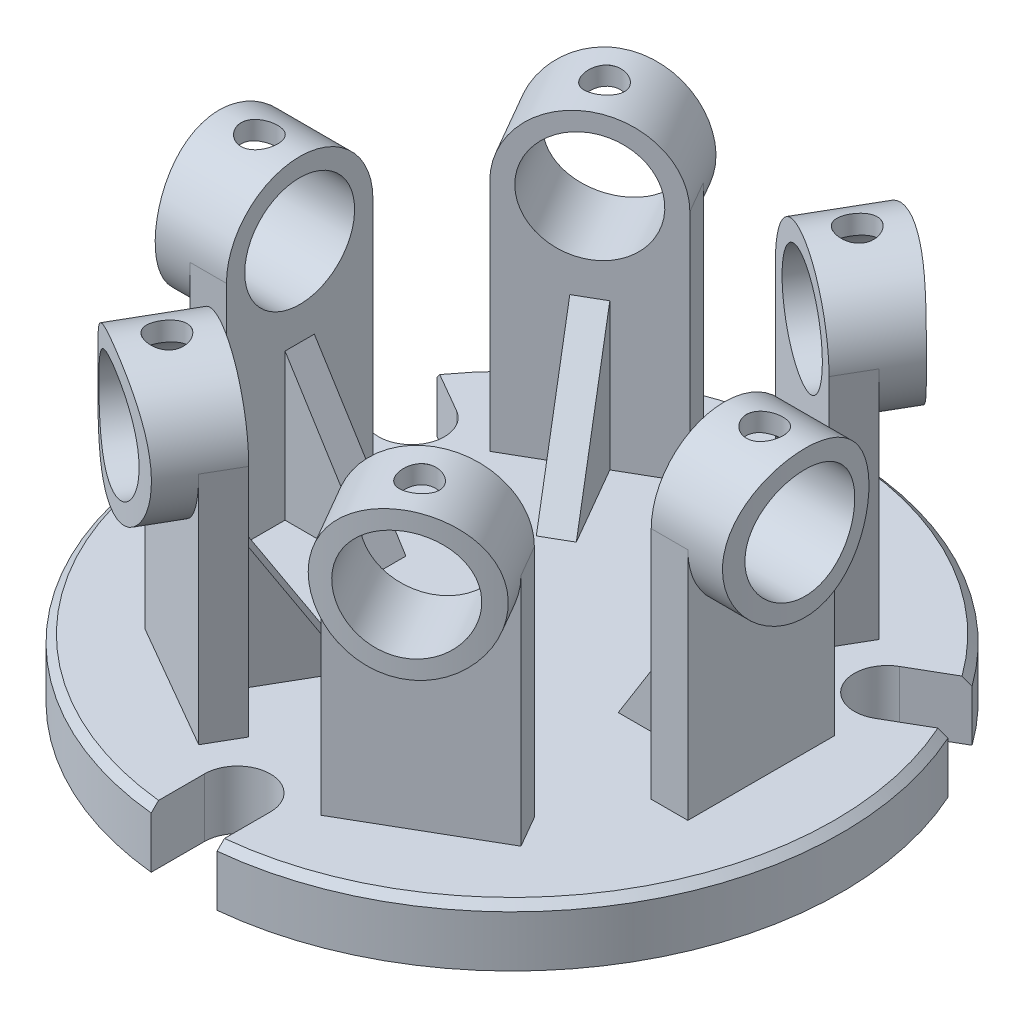
SolidWorks part; units mm, degrees
ref_plane "Front Plane" through (0, 0, 0) normal (0, 0, 1) x (1, 0, 0)
ref_plane "Top Plane" through (0, 0, 0) normal (0, 1, 0) x (1, 0, 0)
ref_plane "Right Plane" through (0, 0, 0) normal (1, 0, 0) x (0, 0, -1)
sketch "Sketch1" plane through (0, 0, 0) normal (0, 1, 0) x (1, 0, 0)
  circle A0 centre (0, 0) radius 90
  dimension "D1" = 180
extrude "Boss-Extrude1" add sketch "Sketch1" along normal blind 16
sketch "Sketch16" plane through (0, 16, 0) normal (0, 1, 0) x (1, 0, 0)
  line L0 (0, 0) -> (0, -90) construction
  line L1 (-9, -75) -> (-9, -89.5489)
  line L2 (9, -75) -> (9, -89.5489)
  circle A0 centre (0, 0) radius 90 construction
  arc A1 (9, -75) -> (-9, -75) centre (0, -75) ccw
  arc A2 (-9, -89.5489) -> (9, -89.5489) centre (0, 0) ccw
  dimension "D1" = 18
  dimension "D2" = 75
extrude "Cut-Extrude4" cut sketch "Sketch16" against normal up to next
pattern_circular "CirPattern12" count 3 over 360 about axis through (0, 16, 0) along (0, -1, 0) of "Cut-Extrude4" reverse direction yes
sketch "Sketch2" plane through (0, 0, 0) normal (0, 0, 1) x (1, 0, 0)
  line L0 (0, 0) -> (-90, 0) construction
  line L2 (-33, 16) -> (-58, 16)
  line L4 (-58, 16) -> (-58, 56)
  line L5 (-58, 56) -> (-33, 16)
  point P2 (-90, 0)
  point P6 (-33, 16)
  dimension "D1" = 16
  dimension "D2" = 25
  dimension "D3" = 40
  dimension "D4" = 58
extrude "Boss-Extrude2" add sketch "Sketch2" along normal blind 4 and the other way blind 4
sketch "Sketch6" plane through (-58, 0, 0) normal (-1, 0, 0) x (0, 0, 1)
  line L1 (-20, 16) -> (-20, 80)
  line L3 (20, 80) -> (20, 16)
  line L5 (0, 0) -> (0, 100) construction
  line L7 (0, 60) -> (20, 60)
  line L8 (0, 60) -> (-20, 60)
  line L9 (-20, 16) -> (20, 16)
  circle A0 centre (0, 80) radius 20
  circle A2 centre (0, 80) radius 20
  circle A3 centre (0, 80) radius 15
  line M10 (-4, 16) -> (4, 16)
  line M11 (4, 16) -> (4, 56)
  line M12 (4, 56) -> (-4, 56)
  line M13 (-4, 56) -> (-4, 16)
  dimension "D3" = 40
  dimension "D4" = 80
  dimension "D5" = 30
  dimension "D1" = 16
  dimension "D2" = 20
extrude "Boss-Extrude6" add sketch "Sketch6" along normal blind 22 contours L5 L9 L3 L7 M12 M11 | L5 L8 L1 L9 M12 M13 | L5 M10 M12 M13 | L5 L9 M11 M12 | A0 L1 L8 | A0 L7 L3 | A0 L5 A3 A2 | L5 A0 A3 region at (-58, 38.4444, -11.7778) region at (-58, 64.4674, -15.5326) region at (-58, 36, -2) region at (-58, 93.8259, -13.8259) region at (-58, 38.4444, 11.7778) region at (-58, 64.4674, 15.5326) region at (-58, 62.5, 0.4472) region at (-58, 36, 2)
sketch "Sketch13" plane through (-80, 0, 0) normal (-1, 0, 0) x (0, 0, 1)
  line L0 (-20, 16) -> (20, 16)
  line L1 (20, 16) -> (20, 80)
  line L2 (20, 80) -> (20, 16) construction
  line L4 (-20, 16) -> (-20, 80) construction
  line L5 (-20, 80) -> (-20, 16)
  arc A0 (-20, 80) -> (20, 80) centre (0, 80) ccw
  point P13 (20, 80)
  point P14 (-20, 80)
extrude "Cut-Extrude3" cut sketch "Sketch13" against normal blind 12
hole_wizard "Ø10.0mm Dowel Hole2" positions "3DSketch2" profile "Sketch15" hole size "Ø10.0" standard "ANSI Metric" end condition up to next
sketch3d "3DSketch2"
  line L0 (-58, 100, 0) -> (-80, 100, 0) construction
  arc A0 (-58, 80, 20) -> (-58, 80, -20) centre (-58, 80, 0) ccw construction
  circle A1 centre (-80, 80, 0) radius 20 construction
  point P0 (-69, 100, 0)
  point P8 (-78, 80, 0)
  point P11 (-100, 80, 0)
sketch "Sketch15" plane through (-69, 100, 0) normal (1, 0, 0) x (0, 0, 1)
  line L0 (0, 0) -> (0, 5)
  line L1 (0, 5) -> (5, 5)
  line L2 (5, 5) -> (5, 0.025)
  line L3 (5, 0.025) -> (5.025, 0)
  line L5 (5.025, 0) -> (0, 0)
  line L6 (-5, 0.025) -> (-5.025, 0) construction
  line L11 (0, -6.35) -> (0, 107.95) construction
  dimension "Thru Hole Dia." = 10
  dimension "Thru Hole Depth" = 5
  dimension "Near C'Sink Dia." = 10.05
  dimension "Near C'Sink Angle" = 90
chamfer "Chamfer2" distance 2 angle 45 3 edges at (77.9423, 16, 45) (-77.9423, 16, 45) (0, 16, -90)
pattern_circular "CirPattern13" count 6 over 360 about axis through (0, 16, 0) along (0, -1, 0) of "Boss-Extrude2", "Boss-Extrude6", "Cut-Extrude3", "Ø10.0mm Dowel Hole2" reverse direction yes
ref_plane "Plane1" through (0, 116, 0) normal (0, 1, 0) x (1, 0, 0)
sketch "Sketch17" plane through (0, 116, 0) normal (0, 1, 0) x (1, 0, 0)
  circle A0 centre (0, 0) radius 90
  circle A1 centre (0, 0) radius 80
  dimension "D1" = 180
  dimension "D2" = 160
extrude "Cut-Extrude5" cut sketch "Sketch17" against normal up to surface (100 mm away) up to face at (-27.125, 16, 46.9819)
